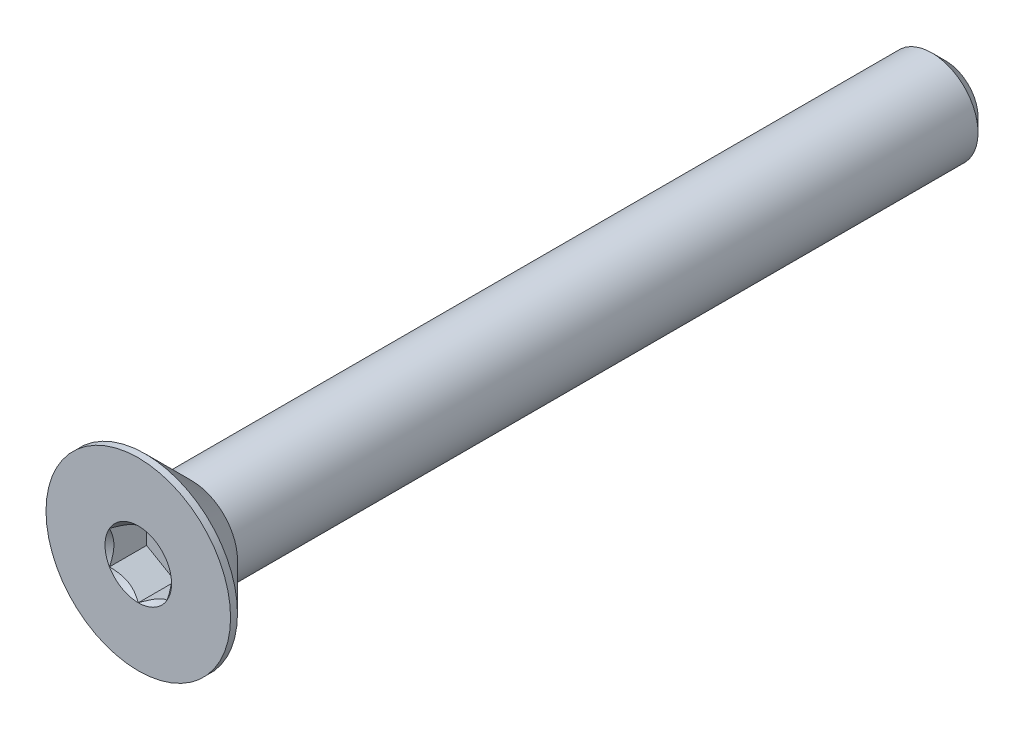
SolidWorks part; units mm, degrees
material "Alloy Steel"
ref_plane "Front" through (0, 0, 0) normal (0, 0, 1) x (1, 0, 0)
ref_plane "Top" through (0, 0, 0) normal (0, 1, 0) x (1, 0, 0)
ref_plane "Right" through (0, 0, 0) normal (1, 0, 0) x (0, 0, -1)
sketch "Sketch1" plane through (0, 0, 0) normal (1, 0, 0) x (0, 0, -1)
  line L0 (-17.5, 4) -> (-17.2, 4) construction
  line L1 (-17.2, 4) -> (-15.2, 2) construction
  line L2 (-17.5, 2) -> (17.5, 2) construction
  line L3 (17.5, 2) -> (17.5, 0) construction
  line L4 (17.5, 0) -> (-17.5, 0) construction
  line L5 (-17.5, 0) -> (-17.5, 4) construction
  line L6 (-17.5, 4) -> (-17.5, -4) construction
  line L7 (17.5, 2) -> (17.5, -2) construction
  line L8 (-17.5, -4) -> (-17.2, -4) construction
  line L9 (-17.2, -4) -> (-15.2, -2) construction
  line L11 (-17.5, 2) -> (-17.5, 0) construction
  line L12 (-15.2, 2) -> (-15.2, 0) construction
  line L13 (17.4563, 2.0758) -> (17.8063, 1.4696) construction
  line L14 (17.8063, 1.4696) -> (18.1563, 2.0758) construction
  line L15 (18.1563, 2.0758) -> (17.4563, 2.0758) construction
  line L16 (17.8063, 2.0758) -> (17.8063, 2) construction
  line L17 (17.8063, 2) -> (17.8063, 1.5453) construction
  line L18 (17.8063, 1.5453) -> (17.8063, 1.4696) construction
  line L19 (17.8063, 2.0379) -> (18.1344, 2.0379) construction
  line L20 (17.8063, 2.0379) -> (17.4781, 2.0379) construction
  line L21 (17.5, 2) -> (18.1125, 2) construction
  line L22 (17.7625, 1.5453) -> (17.85, 1.5453) construction
  line L23 (17.5, -2) -> (-15.2, -2) construction
  point P10 (15.75, -2)
  point P24 (-15.2, 2)
  point P30 (0, 0)
  dimension "Head Diameter" = 8
  dimension "Head Height" = 2.3
  dimension "Length" = 35
  dimension "Countersink Angle" = 90
  dimension "Thread Pitch" = 0.7
  dimension "D2" = 0.0875
  dimension "Minimum Thread Length" = 32.7
  dimension "Thread Size" = 4
  dimension "D1" = 1.75
sketch "Sketch2" plane through (0, 0, 0) normal (0, 0, 1) x (1, 0, 0)
  line L1 (0, 1.4434) -> (-1.25, 0.7217) construction
  line L2 (-1.25, 0.7217) -> (-1.25, -0.7217) construction
  line L3 (-1.25, -0.7217) -> (0, -1.4434) construction
  line L4 (0, -1.4434) -> (1.25, -0.7217) construction
  line L5 (1.25, -0.7217) -> (1.25, 0.7217) construction
  line L6 (1.25, 0.7217) -> (0, 1.4434) construction
  circle A0 centre (0, 0) radius 1.25 construction
  dimension "Drive Size" = 2.5
sketch "Sketch3" plane through (0, 0, 0) normal (1, 0, 0) x (0, 0, -1)
  line L0 (-17.5, 2) -> (17.5, 2)
  line L1 (17.5, 2) -> (17.5, 0)
  line L2 (17.5, 0) -> (-17.5, 0)
  line L3 (-17.5, 0) -> (-17.5, 2)
revolve "Revolve1" add sketch "Sketch3" angle 360 about L4
chamfer "Chamfer1" distance 0.6 angle 45 1 edges at (0, 2, -17.5)
sketch "Sketch6" plane through (0, 0, 0) normal (1, 0, 0) x (0, 0, -1)
  line L0 (-17.5, 4) -> (-17.2, 4)
  line L1 (-17.2, 4) -> (-15.2, 2)
  line L2 (-15.2, 2) -> (-15.2, 0)
  line L3 (-15.2, 0) -> (-17.5, 0)
  line L4 (-17.5, 0) -> (-17.5, 4)
revolve "Revolve2" add sketch "Sketch6" angle 360 about L4
sketch "Sketch8" plane through (0, 0, 17.5) normal (0, 0, 1) x (1, 0, 0)
  line L0 (0, 1.4434) -> (-1.25, 0.7217) construction
  line L1 (1.25, 0.7217) -> (0, 1.4434) construction
  line L2 (1.25, -0.7217) -> (1.25, 0.7217) construction
  line L3 (0, -1.4434) -> (1.25, -0.7217) construction
  line L4 (-1.25, 0.7217) -> (-1.25, -0.7217) construction
  line L5 (-1.25, -0.7217) -> (0, -1.4434) construction
  line L6 (0, 1.4434) -> (-1.25, 0.7217)
  line L7 (1.25, 0.7217) -> (0, 1.4434)
  line L8 (1.25, -0.7217) -> (1.25, 0.7217)
  line L9 (0, -1.4434) -> (1.25, -0.7217)
  line L10 (-1.25, 0.7217) -> (-1.25, -0.7217)
  line L11 (-1.25, -0.7217) -> (0, -1.4434)
extrude "Cut-Extrude1" cut sketch "Sketch8" against normal blind 1.61
sketch "Sketch9" plane through (0, 0, 17.5) normal (0, 0, 1) x (1, 0, 0)
  circle A0 centre (0, 0) radius 1.4434
extrude "Cut-Extrude2" cut sketch "Sketch9" against normal up to next (1.61 mm away) draft 45
ref_plane "Plane1" [suppressed] through (0, 0, 15.2) normal (0, 0, 1) x (1, 0, 0)
split "Split1" [suppressed] bodies to split 124
sketch "Sketch4" [suppressed] plane through (0, 0, -17.5) normal (0, 0, -1) x (-1, 0, 0)
  circle A0 centre (0, 0) radius 2 construction
  circle A1 centre (0, 0) radius 2
curve "Helix/Spiral1" [suppressed] pitch 0.7 height 33.4 turns 47.7143
sketch "Sketch10" [suppressed] plane through (0, 0, 0) normal (1, 0, 0) x (0, 0, -1)
  line L0 (17.4781, 2.0379) -> (18.1344, 2.0379)
  line L1 (18.1344, 2.0379) -> (17.85, 1.5453)
  line L2 (17.85, 1.5453) -> (17.7625, 1.5453)
  line L3 (17.7625, 1.5453) -> (17.4781, 2.0379)
sweep "Cut-Sweep1" [suppressed] cut profiles "Sketch10" path "Helix/Spiral1"
equation "\"D2@Sketch1\" = \"Thread Pitch@Sketch1\" / 8"
equation "\"D4@Helix/Spiral1\"=\"Thread Pitch@Sketch1\""
equation "\"D3@Helix/Spiral1\"=\"Minimum Thread Length@Sketch1\"+\"Thread Pitch@Sketch1\""
equation "\"D1@Chamfer1\"=\"Thread Size@Sketch1\"*.15"
equation "\"D1@Cut-Extrude1\"=\"Head Height@Sketch1\"*.7"
equation "\"D1@Sketch1\"=\"Thread Pitch@Sketch1\"*2.5"
